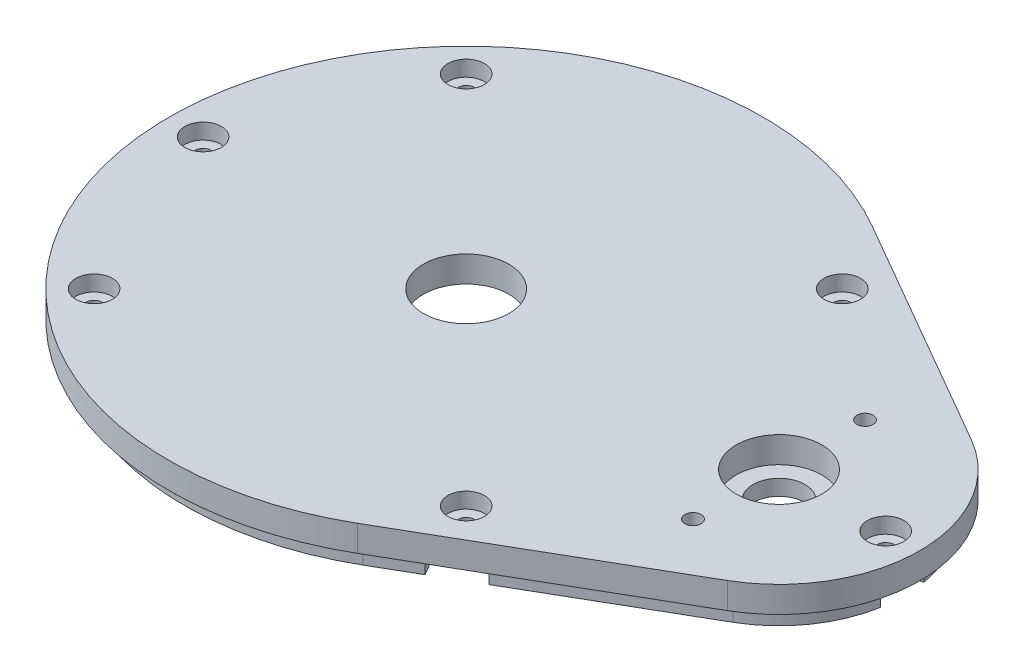
SolidWorks part; units mm, degrees
ref_plane "Front Plane" through (0, 0, 0) normal (0, 0, 1) x (1, 0, 0)
ref_plane "Top Plane" through (0, 0, 0) normal (0, 1, 0) x (1, 0, 0)
ref_plane "Right Plane" through (0, 0, 0) normal (1, 0, 0) x (0, 0, -1)
sketch "Sketch1" plane through (0, 0, 0) normal (0, 1, 0) x (1, 0, 0)
  line L8 (45, -16.5) -> (45, 16.5) construction
  line L9 (13.5, -49.3634) -> (58.5, -23.3827)
  line L10 (13.5, 49.3634) -> (58.5, 23.3827)
  circle A0 centre (-15, 0) radius 46.5 construction
  circle A1 centre (45, 0) radius 16.5 construction
  circle A2 centre (-15, 0) radius 8.2
  circle A3 centre (45, 0) radius 8.2
  circle A4 centre (45, 16.5) radius 1.55
  circle A5 centre (45, -16.5) radius 1.55
  circle A8 centre (-15, 0) radius 57 construction
  circle A9 centre (45, 0) radius 27 construction
  arc A12 (13.5, 49.3634) -> (13.5, -49.3634) centre (-15, 0) ccw
  arc A13 (58.5, 23.3827) -> (58.5, -23.3827) centre (45, 0) cw
  point P0 (0, 0)
  point P17 (45, 0)
  point P18 (45, 0)
extrude "Boss-Extrude1" add sketch "Sketch1" along normal blind 5
sketch "Sketch2" plane through (0, 0, 0) normal (0, -1, 0) x (1, 0, 0)
  circle A0 centre (45, 0) radius 5
  circle A1 centre (45, 0) radius 12
extrude "Boss-Extrude2" add sketch "Sketch2" along normal blind 3
sketch "Sketch4" plane through (0, 0, 0) normal (0, -1, 0) x (1, 0, 0)
  line L1 (12, -46.7654) -> (19.5342, -42.4155)
  line L3 (11, -45.0333) -> (18.5342, -40.6834)
  line L5 (45, 0) -> (68.6354, 4.1676) construction
  line L6 (45, 0) -> (68.6354, -4.1676) construction
  line L8 (68.6354, -4.1676) -> (66.6658, -3.8203)
  line L9 (66.6658, 3.8203) -> (68.6354, 4.1676)
  line L10 (-15, 0) -> (-68.7945, 4.7064) construction
  line L11 (-15, 0) -> (-68.7945, -4.7064) construction
  line L14 (-15, 0) -> (-49.7105, 41.3664) construction
  line L15 (-15, 0) -> (-56.3664, 34.7105) construction
  line L16 (-15, 0) -> (-49.7105, -41.3664) construction
  line L17 (-15, 0) -> (-56.3664, -34.7105) construction
  line L18 (-49.7105, 41.3664) -> (-48.425, 39.8343)
  line L19 (-54.8343, 33.425) -> (-56.3664, 34.7105)
  line L20 (-66.8021, 4.5321) -> (-68.7945, 4.7064)
  line L21 (-68.7945, -4.7064) -> (-66.8021, -4.5321)
  line L22 (-54.8343, -33.425) -> (-56.3664, -34.7105)
  line L23 (-48.425, -39.8343) -> (-49.7105, -41.3664)
  line L24 (57, 20.7846) -> (27.3285, 37.9155)
  line L25 (11, 45.0333) -> (18.5342, 40.6834)
  line L29 (-15, 0) -> (21.0624, 36.0624) construction
  line L30 (17.1653, 38.3124) -> (24.9596, 33.8124) construction
  line L31 (17.1653, 38.3124) -> (19.5342, 42.4155) construction
  line L33 (24.9596, 33.8124) -> (27.3285, 37.9155) construction
  line L34 (26.3285, 36.1834) -> (56, 19.0526)
  line L35 (19.5342, 42.4155) -> (12, 46.7654)
  line L36 (19.5342, 42.4155) -> (18.5342, 40.6834)
  line L37 (27.3285, 37.9155) -> (26.3285, 36.1834)
  line L38 (-15, 0) -> (21.0624, -36.0624) construction
  line L39 (17.1653, -38.3124) -> (24.9596, -33.8124) construction
  line L40 (17.1653, -38.3124) -> (19.5342, -42.4155) construction
  line L41 (24.9596, -33.8124) -> (27.3285, -37.9155) construction
  line L42 (26.3285, -36.1834) -> (56, -19.0526)
  line L43 (27.3285, -37.9155) -> (57, -20.7846)
  line L44 (18.5342, -40.6834) -> (19.5342, -42.4155)
  line L45 (26.3285, -36.1834) -> (27.3285, -37.9155)
  arc A10 (56, 19.0526) -> (66.6658, 3.8203) centre (45, 0) cw
  arc A11 (66.6658, -3.8203) -> (56, -19.0526) centre (45, 0) cw
  arc A12 (57, 20.7846) -> (68.6354, 4.1676) centre (45, 0) cw
  arc A13 (57, -20.7846) -> (68.6354, -4.1676) centre (45, 0) ccw
  arc A18 (12, 46.7654) -> (-49.7105, 41.3664) centre (-15, 0) ccw
  arc A19 (-68.7945, -4.7064) -> (-56.3664, -34.7105) centre (-15, 0) ccw
  arc A20 (11, 45.0333) -> (-48.425, 39.8343) centre (-15, 0) ccw
  arc A21 (-66.8021, -4.5321) -> (-54.8343, -33.425) centre (-15, 0) ccw
  arc A22 (-54.8343, 33.425) -> (-66.8021, 4.5321) centre (-15, 0) ccw
  arc A23 (-56.3664, 34.7105) -> (-68.7945, 4.7064) centre (-15, 0) ccw
  arc A24 (-48.425, -39.8343) -> (11, -45.0333) centre (-15, 0) ccw
  arc A25 (-49.7105, -41.3664) -> (12, -46.7654) centre (-15, 0) ccw
  point P32 (21.0624, 36.0624)
  point P39 (21.0624, -36.0624)
extrude "Boss-Extrude3" add sketch "Sketch4" along normal blind 4
sketch "Sketch5" plane through (0, 5, 0) normal (0, 1, 0) x (1, 0, 0)
  line L0 (-15, 0) -> (-65.45, 0) construction
  line L1 (45, 0) -> (65.45, 0) construction
  line L2 (-15, 0) -> (-50.6735, -35.6735) construction
  line L3 (-15, 0) -> (21.0624, -36.0624) construction
  line L9 (-15, 0) -> (21.0624, 36.0624) construction
  line L11 (-15, 0) -> (45, 0) construction
  line L12 (-15, 0) -> (-50.6735, 35.6735) construction
  circle A18 centre (-65.45, 0) radius 1.55
  circle A21 centre (65.45, 0) radius 1.55
  circle A29 centre (-50.6735, -35.6735) radius 1.55
  circle A33 centre (21.0624, 36.0624) radius 1.55
  circle A35 centre (21.0624, -36.0624) radius 1.55
  circle A36 centre (-50.6735, 35.6735) radius 1.55
  point P39 (-15, 0)
extrude "Cut-Extrude1" cut sketch "Sketch5" against normal blind 5
sketch "Sketch6" plane through (0, 5, 0) normal (0, 1, 0) x (1, 0, 0)
  circle A0 centre (-50.6735, 35.6735) radius 3.5
  circle A1 centre (-65.45, 0) radius 3.5
  circle A2 centre (-50.6735, -35.6735) radius 3.5
  circle A3 centre (21.0624, -36.0624) radius 3.5
  circle A4 centre (21.0624, 36.0624) radius 3.5
  circle A5 centre (65.45, 0) radius 3.5
extrude "Cut-Extrude2" cut sketch "Sketch6" against normal blind 3
